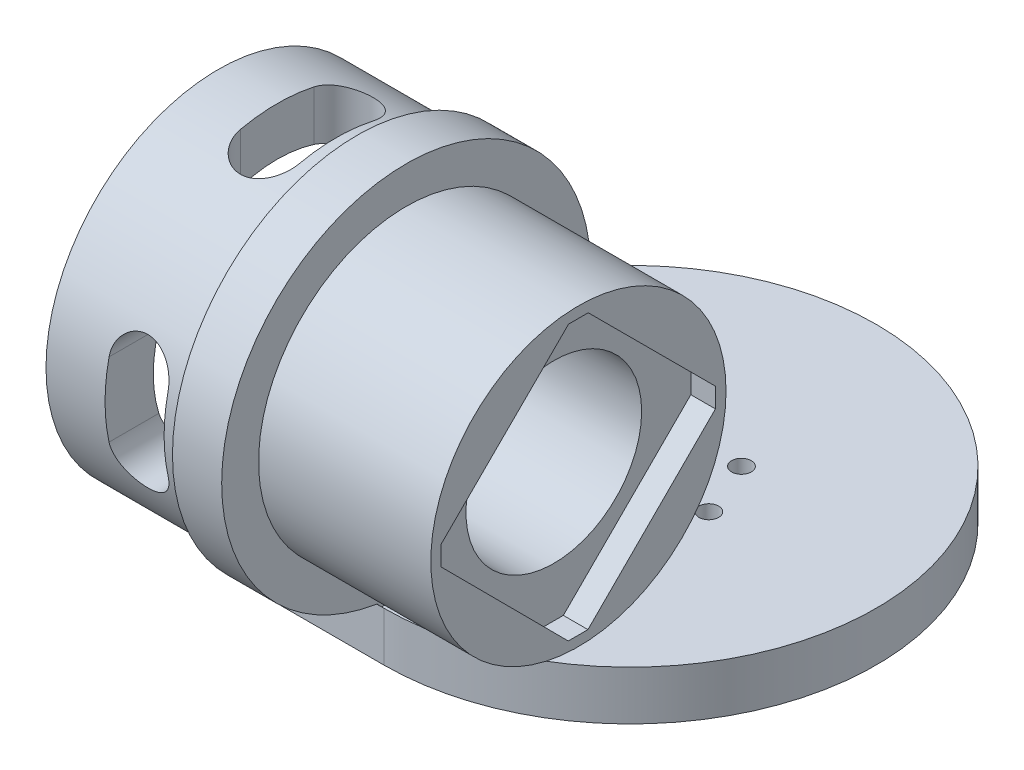
SolidWorks part; units mm, degrees
ref_plane "前视基准面" through (0, 0, 0) normal (0, 0, 1) x (1, 0, 0)
ref_plane "上视基准面" through (0, 0, 0) normal (0, 1, 0) x (1, 0, 0)
ref_plane "右视基准面" through (0, 0, 0) normal (1, 0, 0) x (0, 0, -1)
other "Configuration Table"
sketch "草图1" plane through (0, 0, 0) normal (0, 1, 0) x (1, 0, 0)
  circle A0 centre (0, 0) radius 50
  dimension "D1" = 100
extrude "凸台-拉伸1" add sketch "草图1" along normal blind 10
sketch "草图2" plane through (0, 10, 0) normal (0, 1, 0) x (1, 0, 0)
  circle A0 centre (0, 0) radius 19.85
  circle A1 centre (0, -16) radius 2
  dimension "D2" = 4
  dimension "D1" = 16
extrude "切除-拉伸1" cut sketch "草图2" against normal through all contours A1
pattern_circular "阵列(圆周)1" count 8 over 360 about axis through (0, 10, 0) along (0, 1, 0) of "切除-拉伸1"
ref_plane "基准面1" through (-20, 0, 0) normal (1, 0, 0) x (0, 0, -1)
sketch "草图5" plane through (-20, 0, 0) normal (1, 0, 0) x (0, 0, -1)
sketch "草图6" plane through (-20, 0, 0) normal (1, 0, 0) x (0, 0, -1)
  line L2 (50, 10) -> (-50, 10) construction
  line L3 (-50, 10) -> (-50, 0) construction
  line L4 (-50, 10) -> (-66.5747, 27.1546)
  line L5 (20, 10) -> (-20.7936, 65.7215)
  line L7 (-50, 10) -> (50, 10)
  line L8 (-50, 10) -> (-50, 0)
  line L9 (-50, 0) -> (50, 0)
  line L10 (50, 10) -> (50, 0)
  circle A0 centre (-45, 48) radius 30
  dimension "D1" = 60
  dimension "D2" = 38
  dimension "D3" = 5
  dimension "D4" = 20
extrude "凸台-拉伸4" add sketch "草图6" against normal blind 10 contours A0 | A0 L4 L7 L5 region at (-20, 23.2206, 13.8885) region at (-20, 48, 45)
sketch "草图7" plane through (0, 0, 0) normal (0, -1, 0) x (1, 0, 0)
  line L0 (-30, 50) -> (-44.1176, 23.5294)
  line L1 (-30, 50) -> (-20, 50)
  line L2 (-20, 50) -> (0, 50)
  circle A0 centre (0, 0) radius 50 construction
  circle A2 centre (0, 0) radius 50
  circle A3 centre (0, 0) radius 50
  circle M11 centre (0, 0) radius 50
  dimension "D1" = 0
extrude "凸台-拉伸5" add sketch "草图7" against normal up to surface (10 mm away) contours L2 L1 L0 M11 region at (-26.657, 0, 44.4283) up to face at (-12.4577, 10, -10.0726)
sketch "草图8" plane through (-30, 0, 0) normal (-1, 0, 0) x (0, 0, 1)
  circle A0 centre (45, 48) radius 35
  dimension "D1" = 70
extrude "凸台-拉伸6" add sketch "草图8" against normal up to surface (10 mm away) up to face at (-20, 34.3454, 34.5031)
sketch "草图9" plane through (-30, 0, 0) normal (-1, 0, 0) x (0, 0, 1)
  circle A0 centre (45, 48) radius 25.2
  dimension "D1" = 50.4
extrude "切除-拉伸2" cut sketch "草图9" against normal blind 10
sketch "草图10" plane through (-20, 0, 0) normal (1, 0, 0) x (0, 0, -1)
  circle A0 centre (-45, 48) radius 35
  circle A1 centre (-45, 48) radius 25.2 construction
  circle A2 centre (-45, 48) radius 25.2
extrude "凸台-拉伸7" add sketch "草图10" along normal blind 7.5
sketch "草图11" plane through (-12.5, 0, 0) normal (1, 0, 0) x (0, 0, -1)
  circle A0 centre (-45, 48) radius 15
  circle A1 centre (-45, 48) radius 35
  circle A2 centre (-45, 48) radius 35
  circle A3 centre (-45, 63) radius 1.25
  circle A4 centre (-30, 48) radius 1.25
  circle A5 centre (-60, 48) radius 1.25
  circle A6 centre (-45, 33) radius 1.25
  circle A7 centre (-45, 48) radius 20
  circle A8 centre (-45, 48) radius 35
  circle A9 centre (-45, 48) radius 12
  circle M3 centre (-45, 48) radius 25.2
  dimension "D2" = 2.5
  dimension "D3" = 2.5
  dimension "D4" = 30
  dimension "D5" = 2.5
  dimension "D6" = 2.5
  dimension "D7" = 40
  dimension "D8" = 0
  dimension "D9" = 24
  dimension "D1" = 0
extrude "凸台-拉伸8" add sketch "草图11" along normal blind 7 contours A8 M3 | A7 M3 | A7 A6 A0 A5 A3 A4 | A6 A0 A4 A3 A5 region at (-12.5, 48, 31.6728) region at (-12.5, 48, 79.0101) region at (-12.5, 48, 64.4343) region at (-12.5, 48, 69.4872)
sketch "草图12" plane through (-5.5, 0, 0) normal (1, 0, 0) x (0, 0, -1)
  circle A0 centre (-45, 48) radius 17.85
  circle A1 centre (-45, 48) radius 30
  dimension "D1" = 35.7
  dimension "D2" = 60
extrude "凸台-拉伸9" add sketch "草图12" along normal blind 35
sketch "草图13" plane through (29.5, 0, 0) normal (1, 0, 0) x (0, 0, -1)
  line L1 (-45, 18.3015) -> (-15.3015, 48)
  line L2 (-45, 18.3015) -> (-74.6985, 48)
  line L3 (-74.6985, 48) -> (-45, 77.6985)
  line L4 (-15.3015, 48) -> (-45, 77.6985)
  line L5 (-45, 18.3015) -> (-45, 77.6985) construction
  line L6 (-74.6985, 48) -> (-15.3015, 48) construction
  circle A0 centre (-45, 48) radius 17.85 construction
  circle A1 centre (-45, 48) radius 17.85
  point P0 (-45, 48)
  dimension "D1" = 42
  dimension "D2" = 42
sketch "草图16" plane through (-30, 0, 0) normal (-1, 0, 0) x (0, 0, 1)
  circle A0 centre (45, 48) radius 32.6
  circle A1 centre (45, 48) radius 35
  circle A2 centre (45, 48) radius 34.1
  arc M3 (54.0482, 14.1898) -> (10.1443, 51.1752) centre (45, 48) ccw
  dimension "D1" = 65.2
  dimension "D2" = 68.2
extrude "凸台-拉伸12" add sketch "草图16" along normal blind 7 contours A2 A0 | A1 A2 M3 region at (-30, 26.7493, 72.6855) region at (-30, 48, 11.8645)
sketch "草图17" plane through (-37, 0, 0) normal (-1, 0, 0) x (0, 0, 1)
  circle A0 centre (45, 48) radius 34.1
  circle A1 centre (45, 48) radius 35 construction
  circle A2 centre (45, 48) radius 35
  dimension "D1" = 68.2
extrude "凸台-拉伸13" add sketch "草图17" along normal blind 1.7
sketch "草图18" plane through (0, 0, 50) normal (0, 0, 1) x (1, 0, 0)
  line L0 (-20.7, 55.5) -> (-20.7, 40.5) construction
  line L1 (-14.7, 55.5) -> (-14.7, 40.5)
  line L2 (-26.7, 55.5) -> (-26.7, 40.5)
  line L3 (-38.7, 83) -> (-38.7, 13) construction
  line L4 (-5.5, 83) -> (-38.7, 83) construction
  arc A0 (-14.7, 55.5) -> (-26.7, 55.5) centre (-20.7, 55.5) ccw
  arc A1 (-26.7, 40.5) -> (-14.7, 40.5) centre (-20.7, 40.5) ccw
  point P2 (-20.7, 48)
  dimension "D4" = 35
  dimension "D1" = 18
  dimension "D2" = 12
  dimension "D3" = 15
extrude "切除-拉伸3" cut sketch "草图18" along normal blind 39 contours L2 A1 L1 A0
pattern_circular "阵列(圆周)2" count 2 every 90 about axis through (78.9949, 48, 45) along (-1, 0, 0) of "切除-拉伸3"
sketch "草图19" plane through (-5.5, 0, 0) normal (1, 0, 0) x (0, 0, -1)
  circle A0 centre (-45, 48) radius 30 construction
  circle A1 centre (-45, 48) radius 30
  circle A2 centre (-45, 48) radius 37.5
  dimension "D1" = 75
extrude "凸台-拉伸14" add sketch "草图19" against normal blind 5 and the other way blind 5
sketch "草图21" plane through (-20, 0, 0) normal (1, 0, 0) x (0, 0, -1)
  line L0 (-50, 10) -> (-54.0482, 14.1898)
  line L1 (-25, 10) -> (-20.7891, 22.7249)
  line L4 (50, 10) -> (-50, 10) construction
  line L5 (-50, 10) -> (-25, 10)
  circle A0 centre (-45, 48) radius 35 construction
  circle A1 centre (-45, 48) radius 35
  arc M2 (-10.1443, 51.1752) -> (-54.0482, 14.1898) centre (-45, 48) cw
  line M3 (-54.0482, 14.1898) -> (-50, 10)
  line M4 (-50, 10) -> (20, 10)
  dimension "D1" = 25
extrude "凸台-拉伸15" add sketch "草图21" along normal up to surface (19.5 mm away) contours M2 M3 M4 region at (-20, 13.2836, 34.1598) up to face at (-0.5, 48, 7.5)
sketch "草图22" plane through (29.5, 0, 0) normal (1, 0, 0) x (0, 0, -1)
  line L1 (-74.9106, 48) -> (-45.0003, 77.7693)
  line L2 (-74.9106, 48) -> (-45.0709, 18.0365)
  line L3 (-45.0709, 18.0365) -> (-15.1603, 47.9295)
  line L4 (-45.0003, 77.7693) -> (-15.1603, 47.9295)
  line L5 (-74.9106, 48) -> (-15.1603, 47.9295) construction
  line L6 (-45.0709, 18.0365) -> (-45.0003, 77.7693) construction
  circle A0 centre (-45, 48) radius 30 construction
  circle A1 centre (-45, 48) radius 30
  point P0 (-45.0355, 47.9647)
  dimension "D1" = 42.2
  dimension "D2" = 42.2
extrude "凸台-拉伸16" add sketch "草图22" along normal blind 5
sketch "草图23" plane through (29.5, 0, 0) normal (1, 0, 0) x (0, 0, -1)
  line L0 (-47.005, 75.774) -> (-43.005, 75.774)
  line L1 (-72.91, 49.9911) -> (-72.91, 45.9911)
  line L2 (-17.1609, 49.93) -> (-17.1609, 45.93)
  line L3 (-47.0662, 20.04) -> (-43.0662, 20.04)
  line L4 (-45.0709, 18.0365) -> (-15.1603, 47.9295)
  line L5 (-15.1603, 47.9295) -> (-45.0003, 77.7693)
  line L6 (-45.0003, 77.7693) -> (-74.9106, 48)
  line L7 (-74.9106, 48) -> (-45.0709, 18.0365)
  line L8 (-45.0709, 18.0365) -> (-15.1603, 47.9295)
  line L9 (-15.1603, 47.9295) -> (-45.0003, 77.7693)
  line L10 (-45.0003, 77.7693) -> (-74.9106, 48)
  line L11 (-74.9106, 48) -> (-45.0709, 18.0365)
  line M10 (-45.0709, 18.0365) -> (-15.1603, 47.9295)
  line M11 (-15.1603, 47.9295) -> (-45.0003, 77.7693)
  line M12 (-45.0003, 77.7693) -> (-74.9106, 48)
  line M13 (-74.9106, 48) -> (-45.0709, 18.0365)
  dimension "D2" = 4
  dimension "D3" = 4
  dimension "D4" = 4
  dimension "D5" = 4
  dimension "D1" = 0
extrude "凸台-拉伸17" add sketch "草图23" along normal up to surface (5 mm away) contours L1 M12 M13 | L2 M11 M10 | L0 M12 M11 | L3 M13 M10 region at (29.5, 76.4391, 45.0034) region at (29.5, 47.9941, 73.5769) region at (29.5, 47.9298, 16.494) region at (29.5, 19.3722, 45.0677) up to face at (34.5, 48, 15)
sketch "草图24" plane through (0, 0, 50) normal (0, 0, 1) x (1, 0, 0)
  line L0 (-0.5, 48) -> (34.5, 48)
  line L1 (-0.5, 18) -> (-0.5, 78) construction
  line L2 (34.5, 18) -> (34.5, 78) construction
  line L3 (17, 38) -> (17, 58) construction
  line L4 (14, 38) -> (14, 58)
  line L5 (20, 38) -> (20, 58)
  arc A0 (14, 38) -> (20, 38) centre (17, 38) ccw
  arc A1 (20, 58) -> (14, 58) centre (17, 58) ccw
  point P8 (17, 48)
  dimension "D1" = 3
  dimension "D2" = 20
extrude "切除-拉伸4" [suppressed] cut sketch "草图24" along normal blind 26 contours L5 A1 L4 L0 | L4 A0 L5 L0
pattern_circular "阵列(圆周)3" [suppressed] count 4 over 360 reverse direction yes of bodies 132
